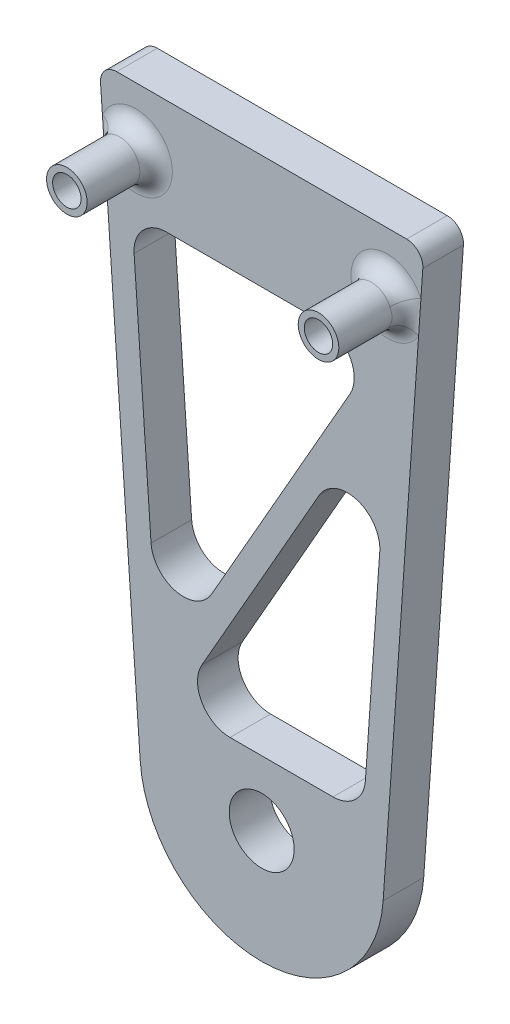
SolidWorks part; units mm, degrees
material "PLA"
ref_plane "Alzado" through (0, 0, 0) normal (0, 0, 1) x (1, 0, 0)
ref_plane "Planta" through (0, 0, 0) normal (0, 1, 0) x (1, 0, 0)
ref_plane "Vista lateral" through (0, 0, 0) normal (1, 0, 0) x (0, 0, -1)
sketch "Croquis1" plane through (0, 0, 0) normal (0, 0, 1) x (1, 0, 0)
  line L0 (0, 0) -> (0, -128.0927) construction
  line L1 (-20.0014, 0) -> (20.0014, 0)
  line L2 (20.0014, 0) -> (14.9635, -72.0463)
  line L3 (-20.0014, 0) -> (-14.9635, -72.0463)
  line L4 (-16.0119, -14.0463) -> (16.0119, -14.0463)
  line L5 (16.0119, -14.0463) -> (12.5155, -64.0463)
  line L6 (12.5155, -64.0463) -> (-12.5155, -64.0463)
  line L7 (-12.5155, -64.0463) -> (-16.0119, -14.0463)
  line L8 (-14.9635, -72.0463) -> (14.9635, -72.0463) construction
  line L9 (-12.7041, -61.35) -> (14.2849, -14.0463)
  line L10 (-12.5155, -64.0463) -> (16.0119, -14.0463) construction
  line L11 (-10.7886, -64.0463) -> (15.7707, -17.496)
  arc A0 (14.9635, -72.0463) -> (-14.9635, -72.0463) centre (0, -71) cw
  circle A1 centre (-15.5, -7.2763) radius 2.5
  circle A2 centre (15.5, -7.2763) radius 2.5
  circle A3 centre (-15.5, -7.2763) radius 1.75
  circle A4 centre (15.5, -7.2763) radius 1.75
  circle A5 centre (0, -72.0463) radius 4
  point P12 (0, -86)
  point P19 (0, -64.0463)
  dimension "D1" = 15
  dimension "D4" = 64.77
  dimension "D5" = 5
  dimension "D7" = 3.5
  dimension "D10" = 8
  dimension "D2" = 86
  dimension "D3" = 86
  dimension "D6" = 31
  dimension "D8" = 3
  dimension "D9" = 50
  dimension "D11" = 8
  dimension "D12" = 3
extrude "Saliente-Extruir1" add sketch "Croquis1" along normal mid plane 5 contours L0 L1 L3 A0 A1 | A1 | A2 | L1 L0 A0 L2 A2 | L6 L11 L5 L4 L9 L7 region at (0, -0.9485, 0) region at (1.6928, -39.1355, 0) region at (-17.9293, -7.2763, 0) region at (13.0707, -7.2763, 0)
extrude "Saliente-Extruir2" add sketch "Croquis1<3>" along normal blind 11 contours A1 | A2 | A3 | A4
sketch "Croquis1<3>" plane through (0, 0, 0) normal (0, 0, 1) x (1, 0, 0) same geometry as "Croquis1"
fillet "Redondeo1" radius 2 2 edges at (18, -7.2763, 2.5) (-13, -7.2763, 2.5)
fillet "Redondeo2" radius 2 2 edges at (20.0014, 0, 0) (-20.0014, 0, 0)
sketch "Croquis2" plane through (0, 0, -2.5) normal (0, 0, -1) x (-1, 0, 0)
  circle A12 centre (-15.5, -7.2763) radius 3
  circle A13 centre (15.5, -7.2763) radius 3
  dimension "D1" = 6
extrude "Cortar-Extruir1" cut sketch "Croquis2" against normal blind 2
fillet "Redondeo3" radius 4 6 edges at (-16.0119, -14.0463, 0) (12.5155, -64.0463, 0) (-10.7886, -64.0463, 0) (-12.7041, -61.35, 0) (14.2849, -14.0463, 0) (15.7707, -17.496, 0)
